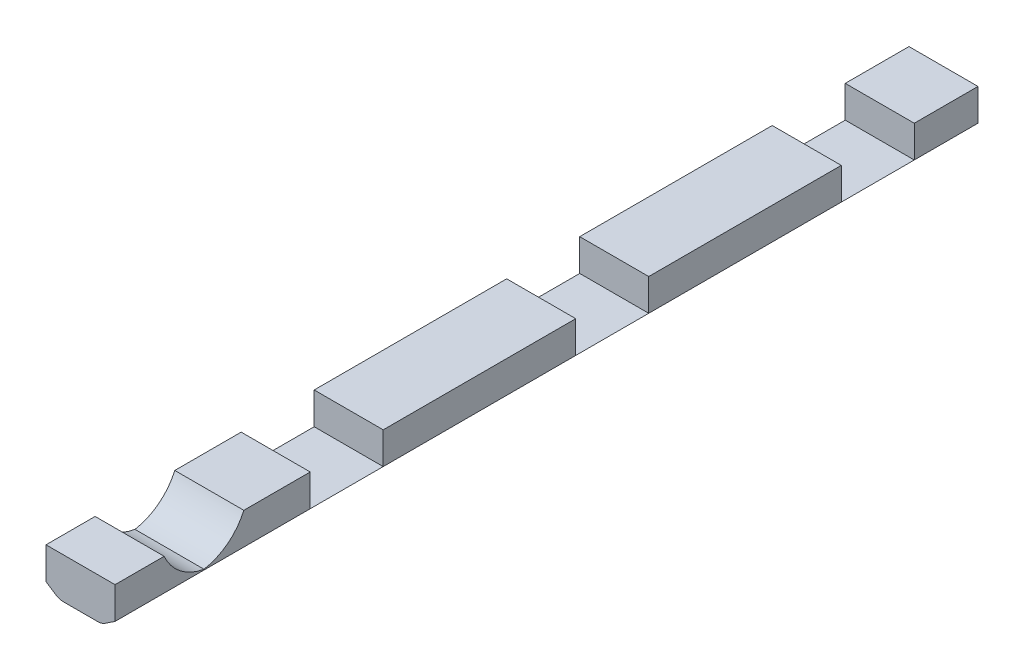
SolidWorks part; units mm, degrees
ref_plane "Front Plane" through (0, 0, 0) normal (0, 0, 1) x (1, 0, 0)
ref_plane "Top Plane" through (0, 0, 0) normal (0, 1, 0) x (1, 0, 0)
ref_plane "Right Plane" through (0, 0, 0) normal (1, 0, 0) x (0, 0, -1)
sketch "Sketch1" plane through (0, 0, 0) normal (0, 0, 1) x (1, 0, 0)
  line L0 (0, 0) -> (3.2, 0)
  line L1 (3.2, 0) -> (4.2, 0.6633)
  line L2 (4.2, 0.6633) -> (4.2, 3.0633)
  line L3 (4.2, 3.0633) -> (-1, 3.0633)
  line L4 (-1, 3.0633) -> (-1, 0.6633)
  line L5 (-1, 0.6633) -> (0, 0)
  dimension "D1" = 5.2
  dimension "D2" = 3.2
  dimension "D3" = 1.2
  dimension "D4" = 2.4
  dimension "D5" = 2.4
  dimension "D6" = 1.2
extrude "Boss-Extrude1" add sketch "Sketch1" along normal blind 65
sketch "Sketch2" plane through (-1, 0, 0) normal (-1, 0, 0) x (0, 0, 1)
  line L0 (65, 3.0633) -> (0, 3.0633) construction
  line L1 (4.8, 3.0633) -> (10.3, 3.0633)
  line L2 (4.8, 3.0633) -> (4.8, 0.6633)
  line L3 (4.8, 0.6633) -> (10.3, 0.6633)
  line L4 (10.3, 3.0633) -> (10.3, 0.6633)
  dimension "D1" = 5.5
  dimension "D2" = 2.4
  dimension "D3" = 4.8
extrude "Cut-Extrude1" cut sketch "Sketch2" against normal blind 6
pattern_linear "LPattern1" count 3 spacing 20 along (0, 0, 1) of "Cut-Extrude1"
sketch "Sketch3" plane through (-1, 0, 0) normal (-1, 0, 0) x (0, 0, 1)
  line L0 (55.3, 3.0633) -> (55.3, 0.6633)
  line L1 (65, 3.0633) -> (50.3, 3.0633) construction
  line L2 (65, 0.6633) -> (50.3, 0.6633) construction
  line L3 (55.3, 0.6633) -> (61.3, 0.6633)
  line L4 (61.3, 0.6633) -> (61.3, 3.0633)
  line L5 (61.3, 3.0633) -> (55.3, 3.0633)
  dimension "D1" = 5
  dimension "D2" = 6
extrude "Cut-Extrude2" cut sketch "Sketch3" against normal blind 6
fillet "Fillet1" radius 4 1 edges at (1.6, 0.6633, 55.3)
fillet "Fillet2" radius 4 1 edges at (1.6, 0.6633, 61.3)
fillet "Fillet3" radius 1 1 edges at (3.2, 0, 32.5)
fillet "Fillet4" radius 1 1 edges at (0, 0, 32.5)
